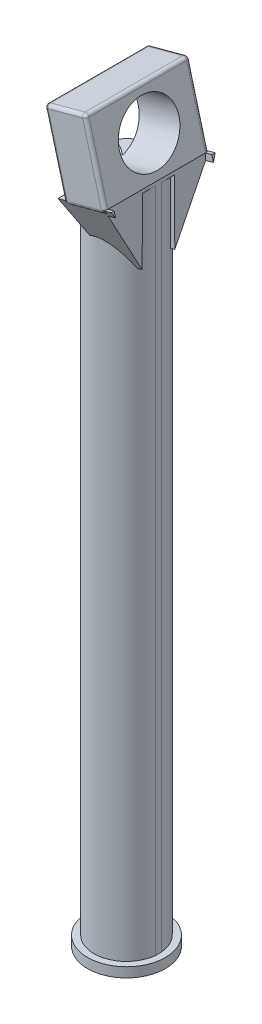
SolidWorks part; units mm, degrees
ref_plane "前视基准面" through (0, 0, 0) normal (0, 0, 1) x (1, 0, 0)
ref_plane "上视基准面" through (0, 0, 0) normal (0, 1, 0) x (1, 0, 0)
ref_plane "右视基准面" through (0, 0, 0) normal (1, 0, 0) x (0, 0, -1)
sketch "草图1" plane through (0, 0, 0) normal (0, 1, 0) x (1, 0, 0)
  circle A0 centre (0, 0) radius 15
  circle A1 centre (0, 0) radius 10
  circle A2 centre (12, 0) radius 1.0704
  circle A3 centre (-12, 0) radius 1.0704
  circle A4 centre (0, 12) radius 1.0704
  circle A5 centre (0, -12) radius 1.0704
  dimension "D1" = 24
  dimension "D2" = 12
  dimension "D3" = 12
  dimension "D4" = 24
extrude "凸台-拉伸2" add sketch "草图1" along normal blind 3
sketch "草图3" plane through (0, 3, 0) normal (0, 1, 0) x (1, 0, 0)
  circle A0 centre (0, 0) radius 10
extrude "凸台-拉伸7" add sketch "草图3" along normal blind 220.7665 and the other way blind 3
sketch "草图5" plane through (0, 223.7665, 0) normal (0, 1, 0) x (1, 0, 0)
  line L0 (10.2225, 13.8518) -> (10.2225, -15.1549) construction
ref_plane "基准面2" through (-55.2568, 206.2214, 0) normal (-0.2588, 0.9659, 0) x (0, 0, 1)
ref_plane "基准面3" through (65.4793, 17.5451, 0) normal (-0.9659, -0.2588, 0) x (0, 0, 1)
sketch "草图6" plane through (65.4793, 17.5451, 0) normal (-0.9659, -0.2588, 0) x (0, 0, 1)
  line L0 (-15.4651, 213.4961) -> (16.6849, 213.4961)
  line L1 (-15.4651, 213.4961) -> (-15.4651, 238.0391)
  line L2 (16.6849, 213.4961) -> (16.6849, 238.0391)
  line L3 (-15.4651, 238.0391) -> (16.6849, 238.0391)
  line L4 (15.9537, 213.4961) -> (-15.9537, 213.4961) construction
extrude "凸台-拉伸8" add sketch "草图6" along normal blind 13
sketch "草图7" plane through (65.4793, 17.5451, 0) normal (0.9659, 0.2588, 0) x (0, 0, -1)
  circle A0 centre (0, 225.9966) radius 9.2
extrude "切除-拉伸1" cut sketch "草图7" against normal blind 44
sketch "草图8" plane through (0, 223.7665, 0) normal (0, 1, 0) x (1, 0, 0)
  line L0 (-8.6868, 5.0622) -> (-8.6081, -5.0892)
  line L1 (-8.6868, 5.0622) -> (-12.7982, 5.0303)
  line L2 (-8.6081, -5.0892) -> (-12.7196, -5.1211)
  line L3 (-12.7982, 5.0303) -> (-12.7196, -5.1211)
  line L4 (-8.6868, -16.6849) -> (-8.6868, 15.4651) construction
  arc A0 (-8.5811, 5.1346) -> (-8.5811, -5.1346) centre (0, 0) ccw construction
  circle A1 centre (0, 0) radius 10 construction
extrude "切除-拉伸2" cut sketch "草图8" against normal blind 218
fillet "圆角1" radius 1 4 edges at (-2.4082, 245.791, 16.6849) (-8.6868, 244.1086, 0.6099) (-2.4082, 245.791, -15.4651) (3.8703, 247.4733, 0.6099)
fillet "圆角2" radius 1 11 edges at (3.6632, 247.1146, -15.1723) (-8.328, 243.9015, -15.1723) (-8.328, 243.9015, 16.392) (3.6632, 247.1146, 16.392) (3.944, 222.0842, -15.4651) (7.1758, 235.1369, -15.4651) (-5.3812, 231.7723, -15.4651) (3.944, 222.0842, 16.6849) (-5.3812, 231.7723, 16.6849) (7.1758, 235.1369, 16.6849) (-2.3345, 220.4019, 13.2043)
fillet "圆角3" radius 1 2 edges at (-2.1274, 220.7606, -15.1723) (-2.3345, 220.4019, -12.0944)
sketch "草图9" plane through (65.4793, 17.5451, 0) normal (-0.9659, -0.2588, 0) x (0, 0, 1)
  line L0 (-15.4651, 214.5214) -> (-4.84, 214.5214)
  line L1 (-15.4651, 214.4961) -> (-15.4651, 237.0391) construction
  line L2 (-4.84, 214.5214) -> (-4.9553, 194.2092)
  line L3 (-4.9553, 218.2452) -> (-4.9553, 7.8181) construction
  line L4 (-4.9553, 194.2092) -> (-15.4651, 214.5214)
  line L5 (16.6194, 214.5214) -> (5.0799, 214.5214)
  line L6 (5.0799, 214.5214) -> (5.0892, 193.8043)
  line L7 (5.0892, 7.798) -> (5.0892, 218.3325) construction
  line L8 (5.0892, 193.8043) -> (16.6194, 214.5214)
extrude "凸台-拉伸9" add sketch "草图9" against normal blind 2 and the other way blind 15
sketch "草图10" plane through (0, 3, 0) normal (0, 1, 0) x (1, 0, 0)
  line L0 (9.9571, -15.6849) -> (9.9571, 14.4651)
  line L1 (9.9571, -15.6849) -> (18.5725, -15.6849)
  line L2 (9.9571, 14.4651) -> (18.5725, 14.4651)
  line L3 (18.5725, -15.6849) -> (18.5725, 14.4651)
  line L4 (9.9571, 14.4651) -> (4.1291, 14.4651) construction
  ellipse E0 centre (8.9912, -15.6849) end of major axis (8.9912, -14.6849) minor radius 0.9659 (9.335, -16.6194) -> (9.9571, -15.6849) ccw construction
extrude "切除-拉伸3" cut sketch "草图10" along normal blind 265
sketch "草图12" plane through (-8.647, 0, 0.067) normal (-1, 0, 0.0077) x (0.0077, 0, 1)
  line L0 (-19.3297, 0) -> (21.549, 0)
  line L1 (-19.3297, 0) -> (-19.3297, 15)
  line L2 (21.549, 0) -> (21.549, 15)
  line L3 (-19.3297, 15) -> (21.549, 15)
extrude "切除-拉伸4" cut sketch "草图12" against normal blind 111 and the other way blind 10
sketch "草图13" plane through (0, 15, 0) normal (0, -1, 0) x (1, 0, 0)
  circle A0 centre (0, 0) radius 12
extrude "凸台-拉伸10" add sketch "草图13" against normal blind 3
sketch "草图14" plane through (0, 15, 0) normal (0, -1, 0) x (-1, 0, 0)
  circle A0 centre (0, 0) radius 1.49
extrude "切除-拉伸5" cut sketch "草图14" against normal blind 25
